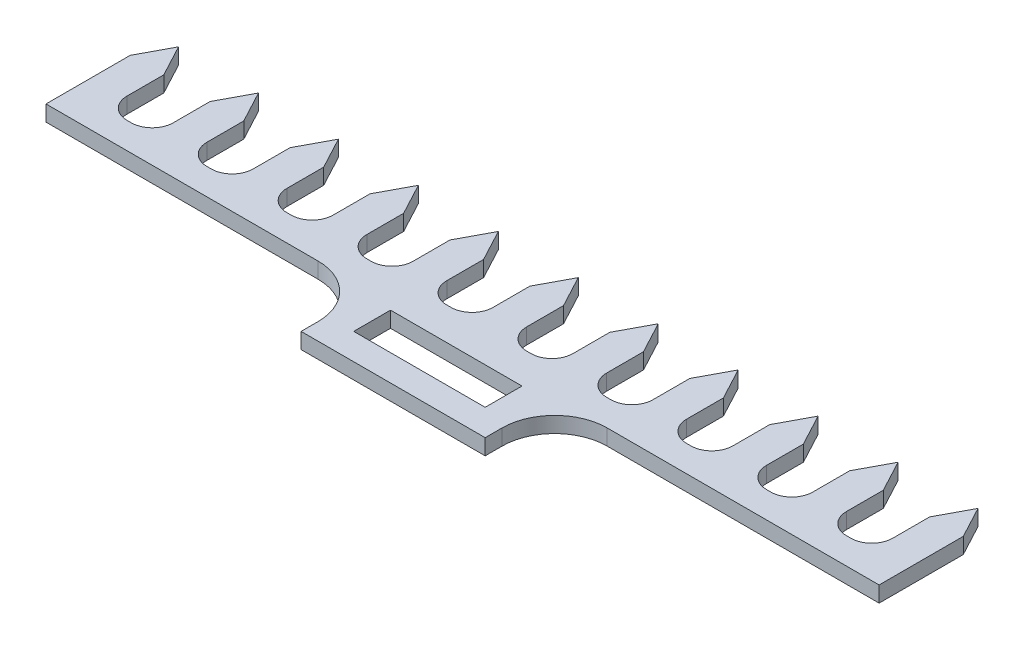
SolidWorks part; units mm, degrees
ref_plane "Front Plane" through (0, 0, 0) normal (0, 0, 1) x (1, 0, 0)
ref_plane "Top Plane" through (0, 0, 0) normal (0, 1, 0) x (1, 0, 0)
ref_plane "Right Plane" through (0, 0, 0) normal (1, 0, 0) x (0, 0, -1)
sketch "Sketch1" plane through (0, 0, 0) normal (0, 1, 0) x (1, 0, 0)
  line L1 (-10.8, 5.1266) -> (-4.4, 5.1266)
  line L2 (-10.8, 5.1266) -> (-10.8, -5.8734)
  line L4 (-4.4, 5.1266) -> (-4.4, -5.8734)
  line L5 (4.4, 5.1266) -> (10.7987, 5.1266)
  line L6 (4.4, 5.1266) -> (4.4, -5.8734)
  line L45 (-4.4, -5.8734) -> (4.4, -5.8734)
  line L46 (-10.8, -5.8734) -> (-10.8, -9.0734)
  line L48 (145.2, -5.8734) -> (145.2, -9.0734)
  line L62 (-4.0013, 5.5907) -> (4.0013, 5.5907) construction
  line L64 (-6.875, 0) -> (6.875, 0) construction
  line L67 (-4.0013, -5.5907) -> (4.0013, -5.5907) construction
  line L68 (10.7987, 5.1266) -> (10.7987, -5.8734)
  line L69 (11.1987, 5.5907) -> (19.2013, 5.5907) construction
  line L70 (11.1987, -5.5907) -> (19.2013, -5.5907) construction
  line L71 (10.7987, -5.8734) -> (19.6, -5.8734)
  line L72 (19.6, -5.8734) -> (19.6, 5.1266)
  line L73 (19.6, 5.1266) -> (26, 5.1266)
  line L74 (26, 5.1266) -> (26, -9.0734)
  line L75 (26, -9.0734) -> (-10.8, -9.0734)
  circle A0 centre (0, 0) radius 4.075 construction
  arc A10 (-4.0013, 5.5907) -> (-4.0013, -5.5907) centre (0, 0) ccw construction
  arc A12 (4.0013, -5.5907) -> (4.0013, 5.5907) centre (0, 0) ccw construction
  arc A13 (19.2013, -5.5907) -> (19.2013, 5.5907) centre (15.2, 0) ccw construction
  arc A14 (11.1987, 5.5907) -> (11.1987, -5.5907) centre (15.2, 0) ccw construction
  dimension "D1" = 8.15
  dimension "D2" = 0.3987
  dimension "D11" = 6.4
  dimension "D4" = 4.4
  dimension "D5" = 13.75
  dimension "D3" = 4.4
  dimension "D6" = 4.4
  dimension "D8" = 6.4
  dimension "D9" = 15.2
  dimension "D10" = 11
  dimension "D12" = 6.3987
  dimension "D7" = 0.4
extrude "Boss-Extrude1" add sketch "Sketch1" along normal blind 3 contours L75 L74 L73 L72 L71 L68 L5 L6 L45 L4 L1 L2 L46 region at (7.5999, 0, 2.9152)
sketch "Sketch2" plane through (0, 3, 0) normal (0, 1, 0) x (1, 0, 0)
  line L0 (-10.8, 5.1266) -> (-7.6, 11.1266)
  line L1 (-7.6, 11.1266) -> (-4.4, 5.1266)
  line L2 (-10.8, 5.1266) -> (-4.4, 5.1266) construction
  line L3 (-10.8, 5.1266) -> (-4.4, 5.1266)
  line L4 (4.4, 5.1266) -> (7.5994, 11.1266)
  line L5 (7.5994, 11.1266) -> (10.7987, 5.1266)
  line L6 (10.7987, 5.1266) -> (4.4, 5.1266)
  line L7 (19.6, 5.1266) -> (22.8, 11.1266)
  line L8 (22.8, 11.1266) -> (26, 5.1266)
  line L9 (26, 5.1266) -> (19.6, 5.1266)
  point P18 (-7.6, 5.1266)
  point P21 (22.8, 5.1266)
  point P23 (7.5994, 5.1266)
  dimension "D1" = 6
extrude "Boss-Extrude2" add sketch "Sketch2" against normal up to surface (3 mm away) up to face at (7.5998, 0, 0.9068)
fillet "Fillet1" radius 4 4 edges at (4.4, 1.5, 5.8734) (19.6, 1.5, 5.8734) (10.7987, 1.5, 5.8734) (-4.4, 1.5, 5.8734)
pattern_linear "LPattern1" count 5 spacing 30.4 along (1, 0, 0) of bodies 102
combine bodies "Combine1" operation type add bodies to combine 102 103 104 105 106
ref_plane "Plane2" through (-10.8, 3, 9.0734) normal (-1, 0, 0) x (0, 0, 1)
sketch "Sketch5" plane through (0, 0, 9.0734) normal (0, 0, 1) x (1, 0, 0)
  line L0 (-10.8, 58) -> (-10.8, -52) construction
  line L1 (147.6, 3) -> (-10.8, 3)
  line L2 (147.6, 3) -> (147.6, 0)
  line L3 (147.6, 0) -> (-10.8, 0)
  line L4 (-10.8, 3) -> (-10.8, 0)
  line L5 (147.6, 0) -> (-10.8, 0) construction
extrude "Boss-Extrude3" add sketch "Sketch5" along normal blind 15
sketch "Sketch6" plane through (0, 3, 0) normal (0, 1, 0) x (1, 0, 0)
  line L0 (147.6, -24.0734) -> (-10.8, -24.0734) construction
  line L1 (55.9, -12.0734) -> (80.9, -12.0734)
  line L2 (55.9, -12.0734) -> (55.9, -19.0734)
  line L3 (55.9, -19.0734) -> (80.9, -19.0734)
  line L4 (80.9, -12.0734) -> (80.9, -19.0734)
  point P4 (68.4, -24.0734)
  point P7 (68.4, -19.0734)
  dimension "D1" = 7
  dimension "D2" = 25
  dimension "D3" = 5
extrude "Cut-Extrude1" cut sketch "Sketch6" against normal blind 60
sketch "Sketch7" plane through (0, 3, 0) normal (0, 1, 0) x (1, 0, 0)
  line L0 (-10.8, 5.1266) -> (-10.8, -24.0734) construction
  line L1 (-10.8, -10.8734) -> (50.9, -10.8734)
  line L2 (-10.8, -10.8734) -> (-10.8, -24.0734)
  line L3 (-10.8, -24.0734) -> (50.9, -24.0734)
  line L4 (50.9, -10.8734) -> (50.9, -24.0734)
  line L5 (147.6, -24.0734) -> (-10.8, -24.0734) construction
  line L6 (55.9, -12.0734) -> (55.9, -19.0734) construction
  line L7 (45.1987, -5.8734) -> (46, -5.8734) construction
  line L8 (68.4, -12.0734) -> (68.4, -24.0734) construction
  line L9 (80.9, -12.0734) -> (55.9, -12.0734) construction
  line L10 (147.6, -24.0734) -> (85.9, -24.0734)
  line L11 (85.9, -10.8734) -> (85.9, -24.0734)
  line L12 (147.6, -10.8734) -> (85.9, -10.8734)
  line L13 (147.6, -10.8734) -> (147.6, -24.0734)
  dimension "D1" = 5
  dimension "D2" = 5
extrude "Cut-Extrude2" cut sketch "Sketch7" against normal blind 10
fillet "Fillet2" radius 10 2 edges at (85.9, 1.5, 10.8734) (50.9, 1.5, 10.8734)
